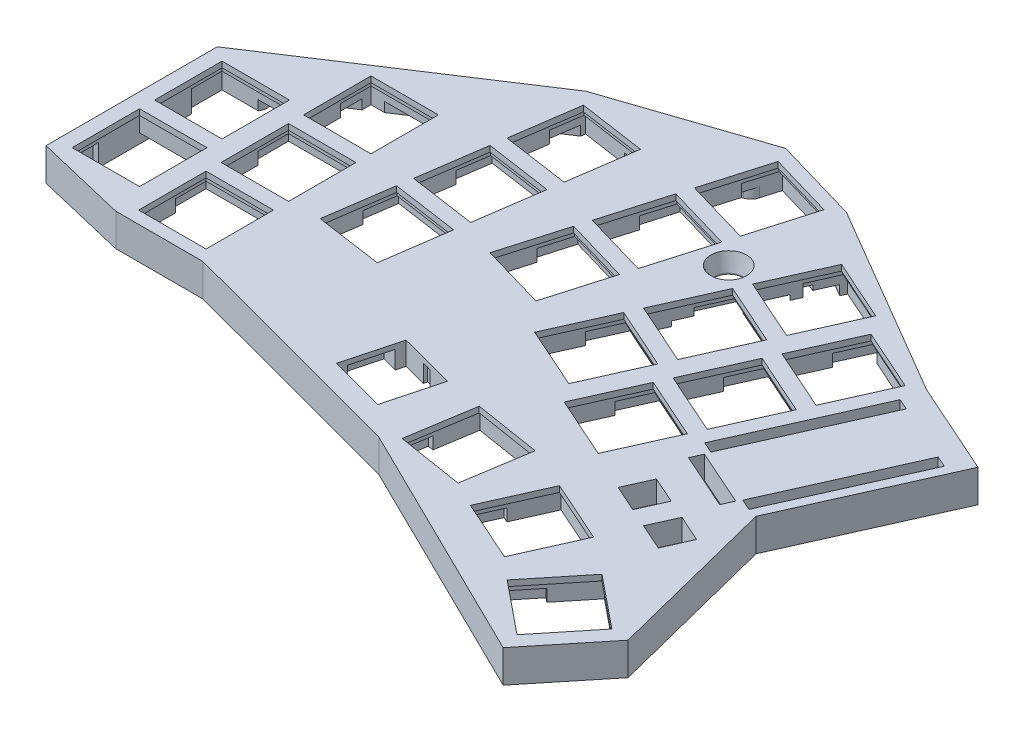
SolidWorks part; units mm, degrees
ref_plane "Front Plane" through (0, 0, 0) normal (0, 0, 1) x (1, 0, 0)
ref_plane "Top Plane" through (0, 0, 0) normal (0, 1, 0) x (1, 0, 0)
ref_plane "Right Plane" through (0, 0, 0) normal (1, 0, 0) x (0, 0, -1)
sketch "Ergogen Drawing" plane through (0, 0, 0) normal (0, 1, 0) x (1, 0, 0)
  line L0 (0.027, 17.9992) -> (18.027, 17.9992)
  line L1 (18.027, 17.9992) -> (18.027, -0.0008)
  line L2 (18.027, -0.0008) -> (0.027, -0.0008)
  line L3 (0.027, -0.0008) -> (0.027, 17.9992)
  line L4 (0.027, 34.9992) -> (18.027, 34.9992)
  line L5 (18.027, 34.9992) -> (18.027, 16.9992)
  line L6 (18.027, 16.9992) -> (0.027, 16.9992)
  line L7 (0.027, 16.9992) -> (0.027, 34.9992)
  line L8 (18.027, 15.9992) -> (36.027, 15.9992)
  line L9 (36.027, 15.9992) -> (36.027, -2.0008)
  line L10 (36.027, -2.0008) -> (18.027, -2.0008)
  line L11 (18.027, -2.0008) -> (18.027, 15.9992)
  line L12 (18.027, 32.9992) -> (36.027, 32.9992)
  line L13 (36.027, 32.9992) -> (36.027, 14.9992)
  line L14 (36.027, 14.9992) -> (18.027, 14.9992)
  line L15 (18.027, 14.9992) -> (18.027, 32.9992)
  line L16 (18.027, 49.9992) -> (36.027, 49.9992)
  line L17 (36.027, 49.9992) -> (36.027, 31.9992)
  line L18 (36.027, 31.9992) -> (18.027, 31.9992)
  line L19 (18.027, 31.9992) -> (18.027, 49.9992)
  line L20 (41.3768, 32.6051) -> (59.3329, 31.3495)
  line L21 (59.3329, 31.3495) -> (58.0773, 13.3933)
  line L22 (58.0773, 13.3933) -> (40.1211, 14.6489)
  line L23 (40.1211, 14.6489) -> (41.3768, 32.6051)
  line L24 (42.5626, 49.5637) -> (60.5188, 48.3081)
  line L25 (60.5188, 48.3081) -> (59.2631, 30.3519)
  line L26 (59.2631, 30.3519) -> (41.307, 31.6075)
  line L27 (41.307, 31.6075) -> (42.5626, 49.5637)
  line L28 (43.7485, 66.5223) -> (61.7046, 65.2667)
  line L29 (61.7046, 65.2667) -> (60.449, 47.3105)
  line L30 (60.449, 47.3105) -> (42.4929, 48.5661)
  line L31 (42.4929, 48.5661) -> (43.7485, 66.5223)
  line L32 (66.0898, 43.7082) -> (83.8507, 40.7838)
  line L33 (83.8507, 40.7838) -> (80.9263, 23.023)
  line L34 (80.9263, 23.023) -> (63.1655, 25.9473)
  line L35 (63.1655, 25.9473) -> (66.0898, 43.7082)
  line L36 (68.8517, 60.4823) -> (86.6126, 57.558)
  line L37 (86.6126, 57.558) -> (83.6882, 39.7971)
  line L38 (83.6882, 39.7971) -> (65.9274, 42.7215)
  line L39 (65.9274, 42.7215) -> (68.8517, 60.4823)
  line L40 (71.6136, 77.2565) -> (89.3745, 74.3321)
  line L41 (89.3745, 74.3321) -> (86.4501, 56.5713)
  line L42 (86.4501, 56.5713) -> (68.6893, 59.4956)
  line L43 (68.6893, 59.4956) -> (71.6136, 77.2565)
  line L44 (88.5581, 32.769) -> (105.9366, 28.0799)
  line L45 (105.9366, 28.0799) -> (101.2475, 10.7014)
  line L46 (101.2475, 10.7014) -> (83.869, 15.3905)
  line L47 (83.869, 15.3905) -> (88.5581, 32.769)
  line L48 (92.9866, 49.182) -> (110.3652, 44.4929)
  line L49 (110.3652, 44.4929) -> (105.6761, 27.1144)
  line L50 (105.6761, 27.1144) -> (88.2976, 31.8035)
  line L51 (88.2976, 31.8035) -> (92.9866, 49.182)
  line L52 (97.4152, 65.595) -> (114.7937, 60.906)
  line L53 (114.7937, 60.906) -> (110.1046, 43.5274)
  line L54 (110.1046, 43.5274) -> (92.7261, 48.2165)
  line L55 (92.7261, 48.2165) -> (97.4152, 65.595)
  line L56 (107.0448, 26.9674) -> (124.0477, 21.0597)
  line L57 (124.0477, 21.0597) -> (118.14, 4.0568)
  line L58 (118.14, 4.0568) -> (101.1371, 9.9645)
  line L59 (101.1371, 9.9645) -> (107.0448, 26.9674)
  line L60 (112.6243, 43.0257) -> (129.6273, 37.118)
  line L61 (129.6273, 37.118) -> (123.7195, 20.1151)
  line L62 (123.7195, 20.1151) -> (106.7166, 26.0228)
  line L63 (106.7166, 26.0228) -> (112.6243, 43.0257)
  line L64 (118.2039, 59.084) -> (135.2068, 53.1763)
  line L65 (135.2068, 53.1763) -> (129.299, 36.1734)
  line L66 (129.299, 36.1734) -> (112.2961, 42.0811)
  line L67 (112.2961, 42.0811) -> (118.2039, 59.084)
  line L68 (95.4197, 6.4051) -> (112.5714, 0.9445)
  line L69 (112.5714, 0.9445) -> (107.1108, -16.2072)
  line L70 (107.1108, -16.2072) -> (89.959, -10.7466)
  line L71 (89.959, -10.7466) -> (95.4197, 6.4051)
  line L72 (116.0129, -0.5249) -> (131.9353, -8.9198)
  line L73 (131.9353, -8.9198) -> (123.5404, -24.8423)
  line L74 (123.5404, -24.8423) -> (107.6179, -16.4473)
  line L75 (107.6179, -16.4473) -> (116.0129, -0.5249)
  line L76 (135.0644, -10.9721) -> (149.2602, -22.0392)
  line L77 (149.2602, -22.0392) -> (138.1931, -36.235)
  line L78 (138.1931, -36.235) -> (123.9973, -25.1679)
  line L79 (123.9973, -25.1679) -> (135.0644, -10.9721)
sketch "Layout Based on OG" plane through (0, 0, 0) normal (0, 1, 0) x (1, 0, 0)
  line L0 (0, 0) -> (0, 17) construction
  line L1 (0, 17) -> (18, 17) construction
  line L2 (18, 17) -> (18, 0) construction
  line L3 (18, 0) -> (0, 0) construction
  line L4 (2.05, 1.55) -> (2.05, 15.45)
  line L5 (2.05, 15.45) -> (15.95, 15.45)
  line L6 (15.95, 15.45) -> (15.95, 1.55)
  line L7 (15.95, 1.55) -> (2.05, 1.55)
  line L8 (109.1798, 58.6066) -> (27, -125.5436) construction
  line L9 (27, 46.7087) -> (27, -125.5436) construction
  line L10 (84.3863, 71.4039) -> (27, -125.5436) construction
  line L11 (54.2678, 62.3831) -> (27, -125.5436) construction
  line L12 (44.7261, 45.0233) -> (58.4821, 43.0274)
  line L13 (2.05, 18.55) -> (15.95, 18.55)
  line L14 (2.05, 18.55) -> (2.05, 32.45)
  line L15 (2.05, 32.45) -> (15.95, 32.45)
  line L16 (15.95, 18.55) -> (15.95, 32.45)
  line L17 (20.05, 31.2587) -> (33.95, 31.2587)
  line L18 (20.05, 31.2587) -> (20.05, 45.1587)
  line L19 (20.05, 45.1587) -> (33.95, 45.1587)
  line L20 (33.95, 31.2587) -> (33.95, 45.1587)
  line L21 (33.95, 28.1587) -> (20.05, 28.1587)
  line L22 (33.95, 28.1587) -> (33.95, 14.2587)
  line L23 (33.95, 14.2587) -> (20.05, 14.2587)
  line L24 (20.05, 28.1587) -> (20.05, 14.2587)
  line L25 (20.05, -2.7413) -> (33.95, -2.7413)
  line L26 (20.05, -2.7413) -> (20.05, 11.1587)
  line L27 (20.05, 11.1587) -> (33.95, 11.1587)
  line L28 (33.95, -2.7413) -> (33.95, 11.1587)
  line L29 (44.7261, 45.0233) -> (42.7302, 31.2674)
  line L30 (58.4821, 43.0274) -> (56.4861, 29.2714)
  line L31 (42.7302, 31.2674) -> (56.4861, 29.2714)
  line L32 (42.285, 28.1995) -> (56.041, 26.2036)
  line L33 (42.285, 28.1995) -> (40.2891, 14.4436)
  line L34 (56.041, 26.2036) -> (54.045, 12.4476)
  line L35 (40.2891, 14.4436) -> (54.045, 12.4476)
  line L36 (47.1672, 61.8472) -> (60.9232, 59.8512)
  line L37 (47.1672, 61.8472) -> (45.1712, 48.0912)
  line L38 (60.9232, 59.8512) -> (58.9272, 46.0953)
  line L39 (45.1712, 48.0912) -> (58.9272, 46.0953)
  line L40 (77.2802, 71.86) -> (90.6252, 67.9716)
  line L41 (77.2802, 71.86) -> (73.3917, 58.515)
  line L42 (90.6252, 67.9716) -> (86.7368, 54.6265)
  line L43 (73.3917, 58.515) -> (86.7368, 54.6265)
  line L44 (85.8695, 51.6503) -> (72.5245, 55.5388)
  line L45 (85.8695, 51.6503) -> (81.9811, 38.3053)
  line L46 (72.5245, 55.5388) -> (68.6361, 42.1937)
  line L47 (81.9811, 38.3053) -> (68.6361, 42.1937)
  line L48 (67.7688, 39.2175) -> (81.1139, 35.329)
  line L49 (67.7688, 39.2175) -> (63.8804, 25.8725)
  line L50 (81.1139, 35.329) -> (77.2254, 21.984)
  line L51 (63.8804, 25.8725) -> (77.2254, 21.984)
  line L52 (102.2015, 60.0235) -> (114.8949, 54.3589)
  line L53 (102.2015, 60.0235) -> (96.5369, 47.3301)
  line L54 (114.8949, 54.3589) -> (109.2302, 41.6655)
  line L55 (96.5369, 47.3301) -> (109.2302, 41.6655)
  line L56 (107.9669, 38.8346) -> (95.2735, 44.4992)
  line L57 (107.9669, 38.8346) -> (102.3023, 26.1412)
  line L58 (95.2735, 44.4992) -> (89.6089, 31.8058)
  line L59 (102.3023, 26.1412) -> (89.6089, 31.8058)
  line L60 (101.039, 23.3103) -> (88.3456, 28.9749)
  line L61 (101.039, 23.3103) -> (95.3744, 10.6169)
  line L62 (88.3456, 28.9749) -> (82.681, 16.2815)
  line L63 (95.3744, 10.6169) -> (82.681, 16.2815)
  line L64 (117.7053, 50.5958) -> (130.3987, 44.9312)
  line L65 (117.7053, 50.5958) -> (112.0407, 37.9024)
  line L66 (130.3987, 44.9312) -> (124.734, 32.2378)
  line L67 (112.0407, 37.9024) -> (124.734, 32.2378)
  line L68 (123.4707, 29.4069) -> (110.7773, 35.0715)
  line L69 (123.4707, 29.4069) -> (117.8061, 16.7135)
  line L70 (110.7773, 35.0715) -> (105.1127, 22.3782)
  line L71 (117.8061, 16.7135) -> (105.1127, 22.3782)
  line L72 (116.5428, 13.8826) -> (103.8494, 19.5473)
  line L73 (116.5428, 13.8826) -> (110.8782, 1.1892)
  line L74 (103.8494, 19.5473) -> (98.1848, 6.8539)
  line L75 (110.8782, 1.1892) -> (98.1848, 6.8539)
  line L76 (90.1692, -2.6429) -> (103.8962, -4.8292)
  line L77 (90.1692, -2.6429) -> (87.9829, -16.3699)
  line L78 (103.8962, -4.8292) -> (101.7099, -18.5562)
  line L79 (87.9829, -16.3699) -> (101.7099, -18.5562)
  line L80 (112.6329, -8.5638) -> (125.3263, -14.2284)
  line L81 (112.6329, -8.5638) -> (106.9683, -21.2572)
  line L82 (125.3263, -14.2284) -> (119.6617, -26.9218)
  line L83 (106.9683, -21.2572) -> (119.6617, -26.9218)
  line L84 (132.8305, -19.9983) -> (143.6253, -28.7552)
  line L85 (132.8305, -19.9983) -> (124.0737, -30.7931)
  line L86 (143.6253, -28.7552) -> (134.8684, -39.55)
  line L87 (124.0737, -30.7931) -> (134.8684, -39.55)
  line L88 (0, 0) -> (0, 34) construction
  line L89 (0, 34) -> (18, 46.7087) construction
  line L90 (18, 46.7087) -> (45.361, 63.6755) construction
  line L91 (45.361, 63.6755) -> (75.7456, 73.9216) construction
  line L92 (75.7456, 73.9216) -> (93.027, 68.8862) construction
  line L93 (93.027, 68.8862) -> (117.3986, 54.9389) construction
  line L94 (117.3986, 54.9389) -> (132.9024, 45.5112) construction
  line L95 (146.1938, -28.843) -> (135.484, -42.0452) construction
  line L96 (135.484, -42.0452) -> (85.7146, -17.5782) construction
  line L97 (0, 0) -> (18, -4.2913) construction
  line L98 (132.9024, 45.5112) -> (119.0465, 14.4627) construction
  line L99 (18, -4.2913) -> (36, -4.2913) construction
  line L100 (36, -4.2913) -> (85.7146, -17.5782) construction
  line L101 (119.0465, 14.4627) -> (137.3104, 6.3121) construction
  line L102 (137.3104, 6.3121) -> (151.1662, 37.3607) construction
  line L103 (151.1662, 37.3607) -> (132.9024, 45.5112) construction
  line L104 (146.1938, -28.843) -> (137.3104, 6.3121) construction
  line L105 (137.3104, 6.3121) -> (151.1662, 37.3607) construction
  line L106 (151.1662, 37.3607) -> (132.9024, 45.5112) construction
  line L107 (119.9597, 14.0551) -> (132.3892, 41.9075)
  line L108 (132.3892, 41.9075) -> (134.6722, 40.8887)
  line L109 (134.6722, 40.8887) -> (122.2427, 13.0363)
  line L110 (122.2427, 13.0363) -> (119.9597, 14.0551)
  line L111 (136.3972, 6.7197) -> (148.8267, 34.5721)
  line L112 (148.8267, 34.5721) -> (146.5437, 35.5909)
  line L113 (146.5437, 35.5909) -> (134.1142, 7.7385)
  line L114 (134.1142, 7.7385) -> (136.3972, 6.7197)
  line L115 (79.4058, -12.7868) -> (67.8127, -9.6883)
  line L116 (67.8127, -9.6883) -> (70.8336, 1.6149)
  line L117 (70.8336, 1.6149) -> (82.4267, -1.4835)
  line L118 (82.4267, -1.4835) -> (79.4058, -12.7868)
  line L119 (97.0327, -3.7361) -> (94.8464, -17.4631) construction
  line L120 (118.9913, -2.8379) -> (121.4364, 2.6412)
  line L121 (121.4364, 2.6412) -> (126.9156, 0.1961)
  line L122 (76.6302, 0.0657) -> (73.6092, -11.2375) construction
  line L123 (126.9156, 0.1961) -> (124.4704, -5.2831)
  line L124 (124.4704, -5.2831) -> (118.9913, -2.8379)
  line L125 (128.4611, -7.064) -> (130.9062, -1.5848)
  line L126 (130.9062, -1.5848) -> (136.3854, -4.03)
  line L127 (136.3854, -4.03) -> (133.9402, -9.5091)
  line L128 (133.9402, -9.5091) -> (128.4611, -7.064)
  line L137 (124.176, 1.4187) -> (121.7308, -4.0605) construction
  line L138 (133.6458, -2.8074) -> (131.2006, -8.2865) construction
  line L139 (126.7317, 7.1456) -> (128.1784, 10.3874) construction
  line L140 (135.0103, 42.8732) -> (147.795, 37.1678) construction
  line L141 (147.795, 37.1678) -> (133.1241, 4.2929) construction
  line L142 (133.1241, 4.2929) -> (120.3393, 9.9982) construction
  line L143 (120.3393, 9.9982) -> (135.0103, 42.8732) construction
  line L144 (120.9329, 9.7333) -> (121.9517, 12.0163)
  line L145 (121.9517, 12.0163) -> (133.5493, 6.8407)
  line L146 (133.5493, 6.8407) -> (132.5305, 4.5578)
  line L147 (132.5305, 4.5578) -> (120.9329, 9.7333)
  line L148 (126.9156, 0.1961) -> (140.3735, -5.8097) construction
  line L164 (-1, 34.5181) -> (-1, -0.7896)
  line L165 (-1, -0.7896) -> (17.8824, -5.2913)
  line L166 (17.8824, -5.2913) -> (35.8687, -5.2913)
  line L167 (35.8687, -5.2913) -> (85.3615, -18.5189)
  line L168 (85.3615, -18.5189) -> (135.7583, -43.2944)
  line L169 (135.7583, -43.2944) -> (147.2861, -29.0838)
  line L170 (147.2861, -29.0838) -> (138.3648, 6.2211)
  line L171 (138.3648, 6.2211) -> (152.487, 37.8664)
  line L172 (152.487, 37.8664) -> (133.3678, 46.3986)
  line L173 (133.3678, 46.3986) -> (117.9068, 55.8002) construction
  line L174 (117.9068, 55.8002) -> (93.4207, 69.8131) construction
  line L175 (93.4207, 69.8131) -> (75.7238, 74.9696)
  line L176 (75.7238, 74.9696) -> (44.9321, 64.5862)
  line L177 (44.9321, 64.5862) -> (17.4476, 47.5429) construction
  line L178 (17.4476, 47.5429) -> (-1, 34.5181) construction
  line L179 (-1, 34.5181) -> (44.9321, 64.5862)
  line L180 (133.3678, 46.3986) -> (93.4207, 69.8131)
  line L181 (27, -125.5436) -> (90.7493, 48.2155) construction
  circle A0 centre (143.0056, -24.3895) radius 2 construction
  circle A1 centre (143.0056, -24.3895) radius 1
  circle A2 centre (98.5143, -21.642) radius 2 construction
  circle A3 centre (98.5143, -21.642) radius 1
  circle A6 centre (17.05, -2.0087) radius 2 construction
  circle A7 centre (17.05, -2.0087) radius 1
  circle A8 centre (5.901, 35.45) radius 2 construction
  circle A9 centre (5.901, 35.45) radius 1
  circle A10 centre (72.7535, 70.802) radius 2 construction
  circle A11 centre (72.7535, 70.802) radius 1
  circle A12 centre (145.3286, 37.7757) radius 2 construction
  circle A13 centre (145.3286, 37.7757) radius 1
  circle A14 centre (90.7493, 48.2155) radius 3
  point P10 (110.8277, 18.1304)
  point P11 (117.7557, 33.6547)
  point P128 (75.1197, -5.5859)
  point P129 (95.9395, -10.5996)
  point P146 (127.7505, 9.4285)
  point P148 (128.1784, 10.3874)
  point P150 (122.9534, -1.3209)
  line B0 (18, 29.7087) -> (18, 46.7087) construction
  line B1 (18, 46.7087) -> (36, 46.7087) construction
  line B2 (36, 46.7087) -> (36, 29.7087) construction
  line B3 (36, 29.7087) -> (18, 29.7087) construction
  line B4 (20.05, 31.2587) -> (20.05, 45.1587) construction
  line B5 (20.05, 45.1587) -> (33.95, 45.1587) construction
  line B6 (33.95, 45.1587) -> (33.95, 31.2587) construction
  line B7 (33.95, 31.2587) -> (20.05, 31.2587) construction
  line B8 (18, 12.7087) -> (18, 29.7087) construction
  line B9 (18, 29.7087) -> (36, 29.7087) construction
  line B10 (36, 29.7087) -> (36, 12.7087) construction
  line B11 (36, 12.7087) -> (18, 12.7087) construction
  line B12 (20.05, 14.2587) -> (20.05, 28.1587) construction
  line B13 (20.05, 28.1587) -> (33.95, 28.1587) construction
  line B14 (33.95, 28.1587) -> (33.95, 14.2587) construction
  line B15 (33.95, 14.2587) -> (20.05, 14.2587) construction
  line B16 (18, -4.2913) -> (18, 12.7087) construction
  line B17 (18, 12.7087) -> (36, 12.7087) construction
  line B18 (36, 12.7087) -> (36, -4.2913) construction
  line B19 (36, -4.2913) -> (18, -4.2913) construction
  line B20 (20.05, -2.7413) -> (20.05, 11.1587) construction
  line B21 (20.05, 11.1587) -> (33.95, 11.1587) construction
  line B22 (33.95, 11.1587) -> (33.95, -2.7413) construction
  line B23 (33.95, -2.7413) -> (20.05, -2.7413) construction
  line B24 (42.9199, 46.8516) -> (45.361, 63.6755) construction
  line B25 (45.361, 63.6755) -> (63.1745, 61.0908) construction
  line B26 (63.1745, 61.0908) -> (60.7334, 44.267) construction
  line B27 (60.7334, 44.267) -> (42.9199, 46.8516) construction
  line B28 (45.1712, 48.0912) -> (47.1672, 61.8472) construction
  line B29 (47.1672, 61.8472) -> (60.9232, 59.8512) construction
  line B30 (60.9232, 59.8512) -> (58.9272, 46.0953) construction
  line B31 (58.9272, 46.0953) -> (45.1712, 48.0912) construction
  line B32 (40.4788, 30.0278) -> (42.9199, 46.8516) construction
  line B33 (42.9199, 46.8516) -> (60.7334, 44.267) construction
  line B34 (60.7334, 44.267) -> (58.2923, 27.4431) construction
  line B35 (58.2923, 27.4431) -> (40.4788, 30.0278) construction
  line B36 (42.7302, 31.2674) -> (44.7261, 45.0233) construction
  line B37 (44.7261, 45.0233) -> (58.4821, 43.0274) construction
  line B38 (58.4821, 43.0274) -> (56.4861, 29.2714) construction
  line B39 (56.4861, 29.2714) -> (42.7302, 31.2674) construction
  line B40 (38.0377, 13.204) -> (40.4788, 30.0278) construction
  line B41 (40.4788, 30.0278) -> (58.2923, 27.4431) construction
  line B42 (58.2923, 27.4431) -> (55.8512, 10.6193) construction
  line B43 (55.8512, 10.6193) -> (38.0377, 13.204) construction
  line B44 (40.2891, 14.4436) -> (42.285, 28.1995) construction
  line B45 (42.285, 28.1995) -> (56.041, 26.2036) construction
  line B46 (56.041, 26.2036) -> (54.045, 12.4476) construction
  line B47 (54.045, 12.4476) -> (40.2891, 14.4436) construction
  line B48 (70.99, 57.6004) -> (75.7456, 73.9216) construction
  line B49 (75.7456, 73.9216) -> (93.027, 68.8862) construction
  line B50 (93.027, 68.8862) -> (88.2713, 52.5649) construction
  line B51 (88.2713, 52.5649) -> (70.99, 57.6004) construction
  line B52 (73.3917, 58.515) -> (77.2802, 71.86) construction
  line B53 (77.2802, 71.86) -> (90.6252, 67.9716) construction
  line B54 (90.6252, 67.9716) -> (86.7368, 54.6265) construction
  line B55 (86.7368, 54.6265) -> (73.3917, 58.515) construction
  line B56 (66.2343, 41.2791) -> (70.99, 57.6004) construction
  line B57 (70.99, 57.6004) -> (88.2713, 52.5649) construction
  line B58 (88.2713, 52.5649) -> (83.5156, 36.2437) construction
  line B59 (83.5156, 36.2437) -> (66.2343, 41.2791) construction
  line B60 (68.6361, 42.1937) -> (72.5245, 55.5388) construction
  line B61 (72.5245, 55.5388) -> (85.8695, 51.6503) construction
  line B62 (85.8695, 51.6503) -> (81.9811, 38.3053) construction
  line B63 (81.9811, 38.3053) -> (68.6361, 42.1937) construction
  line B64 (61.4786, 24.9578) -> (66.2343, 41.2791) construction
  line B65 (66.2343, 41.2791) -> (83.5156, 36.2437) construction
  line B66 (83.5156, 36.2437) -> (78.76, 19.9224) construction
  line B67 (78.76, 19.9224) -> (61.4786, 24.9578) construction
  line B68 (63.8804, 25.8725) -> (67.7688, 39.2175) construction
  line B69 (67.7688, 39.2175) -> (81.1139, 35.329) construction
  line B70 (81.1139, 35.329) -> (77.2254, 21.984) construction
  line B71 (77.2254, 21.984) -> (63.8804, 25.8725) construction
  line B72 (80.1772, 15.7015) -> (87.1052, 31.2258) construction
  line B73 (87.1052, 31.2258) -> (103.5427, 23.8903) construction
  line B74 (103.5427, 23.8903) -> (96.6147, 8.366) construction
  line B75 (96.6147, 8.366) -> (80.1772, 15.7015) construction
  line B76 (82.681, 16.2815) -> (88.3456, 28.9749) construction
  line B77 (88.3456, 28.9749) -> (101.039, 23.3103) construction
  line B78 (101.039, 23.3103) -> (95.3744, 10.6169) construction
  line B79 (95.3744, 10.6169) -> (82.681, 16.2815) construction
  line B80 (87.1052, 31.2258) -> (94.0331, 46.7501) construction
  line B81 (94.0331, 46.7501) -> (110.4706, 39.4146) construction
  line B82 (110.4706, 39.4146) -> (103.5427, 23.8903) construction
  line B83 (103.5427, 23.8903) -> (87.1052, 31.2258) construction
  line B84 (89.6089, 31.8058) -> (95.2735, 44.4992) construction
  line B85 (95.2735, 44.4992) -> (107.9669, 38.8346) construction
  line B86 (107.9669, 38.8346) -> (102.3023, 26.1412) construction
  line B87 (102.3023, 26.1412) -> (89.6089, 31.8058) construction
  line B88 (94.0331, 46.7501) -> (100.9611, 62.2744) construction
  line B89 (100.9611, 62.2744) -> (117.3986, 54.9389) construction
  line B90 (117.3986, 54.9389) -> (110.4706, 39.4146) construction
  line B91 (110.4706, 39.4146) -> (94.0331, 46.7501) construction
  line B92 (96.5369, 47.3301) -> (102.2015, 60.0235) construction
  line B93 (102.2015, 60.0235) -> (114.8949, 54.3589) construction
  line B94 (114.8949, 54.3589) -> (109.2302, 41.6655) construction
  line B95 (109.2302, 41.6655) -> (96.5369, 47.3301) construction
  line B96 (109.5369, 37.3224) -> (116.4649, 52.8467) construction
  line B97 (116.4649, 52.8467) -> (132.9024, 45.5112) construction
  line B98 (132.9024, 45.5112) -> (125.9744, 29.9869) construction
  line B99 (125.9744, 29.9869) -> (109.5369, 37.3224) construction
  line B100 (112.0407, 37.9024) -> (117.7053, 50.5958) construction
  line B101 (117.7053, 50.5958) -> (130.3987, 44.9312) construction
  line B102 (130.3987, 44.9312) -> (124.734, 32.2378) construction
  line B103 (124.734, 32.2378) -> (112.0407, 37.9024) construction
  line B104 (102.609, 21.7981) -> (109.5369, 37.3224) construction
  line B105 (109.5369, 37.3224) -> (125.9744, 29.9869) construction
  line B106 (125.9744, 29.9869) -> (119.0465, 14.4627) construction
  line B107 (119.0465, 14.4627) -> (102.609, 21.7981) construction
  line B108 (105.1127, 22.3782) -> (110.7773, 35.0715) construction
  line B109 (110.7773, 35.0715) -> (123.4707, 29.4069) construction
  line B110 (123.4707, 29.4069) -> (117.8061, 16.7135) construction
  line B111 (117.8061, 16.7135) -> (105.1127, 22.3782) construction
  line B112 (95.6811, 6.2738) -> (102.609, 21.7981) construction
  line B113 (102.609, 21.7981) -> (119.0465, 14.4627) construction
  line B114 (119.0465, 14.4627) -> (112.1185, -1.0616) construction
  line B115 (112.1185, -1.0616) -> (95.6811, 6.2738) construction
  line B116 (98.1848, 6.8539) -> (103.8494, 19.5473) construction
  line B117 (103.8494, 19.5473) -> (116.5428, 13.8826) construction
  line B118 (116.5428, 13.8826) -> (110.8782, 1.1892) construction
  line B119 (110.8782, 1.1892) -> (98.1848, 6.8539) construction
  line B120 (104.4646, -21.8372) -> (111.3925, -6.3129) construction
  line B121 (111.3925, -6.3129) -> (127.83, -13.6484) construction
  line B122 (127.83, -13.6484) -> (120.9021, -29.1727) construction
  line B123 (120.9021, -29.1727) -> (104.4646, -21.8372) construction
  line B124 (106.9683, -21.2572) -> (112.6329, -8.5638) construction
  line B125 (112.6329, -8.5638) -> (125.3263, -14.2284) construction
  line B126 (125.3263, -14.2284) -> (119.6617, -26.9218) construction
  line B127 (119.6617, -26.9218) -> (106.9683, -21.2572) construction
  line B128 (85.7146, -17.5782) -> (88.3885, -0.7898) construction
  line B129 (88.3885, -0.7898) -> (106.1645, -3.621) construction
  line B130 (106.1645, -3.621) -> (103.4906, -20.4094) construction
  line B131 (103.4906, -20.4094) -> (85.7146, -17.5782) construction
  line B132 (87.9829, -16.3699) -> (90.1692, -2.6429) construction
  line B133 (90.1692, -2.6429) -> (103.8962, -4.8292) construction
  line B134 (103.8962, -4.8292) -> (101.7099, -18.5562) construction
  line B135 (101.7099, -18.5562) -> (87.9829, -16.3699) construction
  line B136 (121.5051, -30.7054) -> (132.215, -17.5031) construction
  line B137 (132.215, -17.5031) -> (146.1938, -28.843) construction
  line B138 (146.1938, -28.843) -> (135.484, -42.0452) construction
  line B139 (135.484, -42.0452) -> (121.5051, -30.7054) construction
  line B140 (124.0737, -30.7931) -> (132.8305, -19.9983) construction
  line B141 (132.8305, -19.9983) -> (143.6253, -28.7552) construction
  line B142 (143.6253, -28.7552) -> (134.8684, -39.55) construction
  line B143 (134.8684, -39.55) -> (124.0737, -30.7931) construction
  line B144 (0, 17) -> (0, 34) construction
  line B145 (0, 34) -> (18, 34) construction
  line B146 (18, 34) -> (18, 17) construction
  line B147 (18, 17) -> (0, 17) construction
  line B148 (2.05, 18.55) -> (2.05, 32.45) construction
  line B149 (2.05, 32.45) -> (15.95, 32.45) construction
  line B150 (15.95, 32.45) -> (15.95, 18.55) construction
  line B151 (15.95, 18.55) -> (2.05, 18.55) construction
  dimension "D46" = 4
  dimension "D47" = 2
  dimension "D48" = 3
  dimension "D52" = 4
  dimension "D53" = 2
  dimension "D54" = 4
  dimension "D55" = 2
  dimension "D57" = 4
  dimension "D58" = 2
  dimension "D60" = 4
  dimension "D61" = 2
  dimension "D63" = 4
  dimension "D64" = 2
  dimension "D51" = 3
  dimension "D83" = 6
  dimension "D1" = 18
  dimension "D2" = 17
  dimension "D3" = 13.9
  dimension "D4" = 13.9
  dimension "D5" = 2.05
  dimension "D6" = 1.55
  dimension "D7" = 205.1378
  dimension "D8" = 201.6553
  dimension "D9" = 189.8947
  dimension "D10" = 8.256
  dimension "D11" = 15
  dimension "D12" = 15
  dimension "D13" = 1.4278
  dimension "D14" = 0.974
  dimension "D15" = 1.5327
  dimension "D16" = 0.6031
  dimension "D17" = 5.9541
  dimension "D18" = 2.5593
  dimension "D19" = 7.805
  dimension "D20" = 7.989
  dimension "D21" = 172.2524
  dimension "D22" = 2.2911
  dimension "D23" = 4.2913
  dimension "D24" = 34
  dimension "D25" = 20
  dimension "D26" = 30.5
  dimension "D27" = 2.5
  dimension "D28" = 1
  dimension "D29" = 2.5
  dimension "D30" = 30.5
  dimension "D31" = 18
  dimension "D32" = 11.7
  dimension "D33" = 12
  dimension "D34" = 3
  dimension "D35" = 21.415
  dimension "D36" = 6
  dimension "D37" = 6
  dimension "D38" = 6
  dimension "D39" = 6
  dimension "D40" = 14
  dimension "D41" = 36
  dimension "D42" = 12.7
  dimension "D43" = 2.5
  dimension "D44" = 9.27
  dimension "D45" = 4.37
  dimension "D49" = 3
  dimension "D50" = 3
  dimension "D56" = 3
  dimension "D59" = 3
  dimension "D62" = 3
  dimension "D65" = 3
  dimension "D66" = 3
  dimension "D67" = 1
  dimension "D68" = 1
  dimension "D69" = 1
  dimension "D70" = 1
  dimension "D71" = 1
  dimension "D72" = 1
  dimension "D73" = 1
  dimension "D74" = 1
  dimension "D75" = 1
  dimension "D76" = 1
  dimension "D77" = 1
  dimension "D78" = 1
  dimension "D79" = 1
  dimension "D80" = 1
  dimension "D81" = 1
  dimension "D82" = 3.902
sketch_block_instance "Block-ChocSwitchCutout-3"
sketch_block "Block-ChocSwitchCutout" parameters "D1"=18, "D2"=17, "D3"=13.9, "D4"=13.9, "D5"=2.05, "D6"=1.55
sketch_block_instance "Block-ChocSwitchCutout-4"
sketch_block_instance "Block-ChocSwitchCutout-5"
sketch_block_instance "Block-ChocSwitchCutout-6"
sketch_block_instance "Block-ChocSwitchCutout-7"
sketch_block_instance "Block-ChocSwitchCutout-8"
sketch_block_instance "Block-ChocSwitchCutout-9"
sketch_block_instance "Block-ChocSwitchCutout-10"
sketch_block_instance "Block-ChocSwitchCutout-11"
sketch_block_instance "Block-ChocSwitchCutout-20"
sketch_block_instance "Block-ChocSwitchCutout-23"
sketch_block_instance "Block-ChocSwitchCutout-24"
sketch_block_instance "Block-ChocSwitchCutout-27"
sketch_block_instance "Block-ChocSwitchCutout-28"
sketch_block_instance "Block-ChocSwitchCutout-29"
sketch_block_instance "Block-ChocSwitchCutout-32"
sketch_block_instance "Block-ChocSwitchCutout-33"
sketch_block_instance "Block-ChocSwitchCutout-34"
sketch_block_instance "Block-ChocSwitchCutout-37"
other "AlignGroup1"
extrude "Top Plate" add sketch "Layout Based on OG" along normal blind 1.2 contours L105 L106 L94 L93 L92 L91 L90 L89 L88 L97 L99 L100 L96 L95 L104 L73 L75 L74 L72 L69 L71 L70 L68 L61 L63 L62 L60 L57 L59 L58 L56 L45 L47 L46 L44 L6 L7 L4 L5 L16 L13 L14 L15 | A9 | A7 | A3 | A1 | A13 | A11 region at (81.1816, 0, -18.7966) region at (143.0056, 0, 24.3895) region at (98.5143, 0, 21.642) region at (17.05, 0, 2.0087) region at (5.901, 0, -35.45) region at (72.7535, 0, -70.802) region at (145.3286, 0, -37.7757)
sketch "Sketch1" plane through (0, 0, 0) normal (0, -1, 0) x (1, 0, 0)
  line L0 (124.9363, -31.7095) -> (130.927, -45.1335)
  line L1 (130.927, -45.1335) -> (117.503, -51.1241)
  line L2 (117.503, -51.1241) -> (111.5124, -37.7002)
  line L3 (111.5124, -37.7002) -> (124.9363, -31.7095)
  line L4 (118.0084, -16.1852) -> (123.999, -29.6092)
  line L5 (117.7053, -50.5958) -> (130.3987, -44.9312) construction
  line L6 (123.999, -29.6092) -> (110.5751, -35.5998)
  line L7 (117.7053, -50.5958) -> (112.0407, -37.9024) construction
  line L8 (110.5751, -35.5998) -> (104.5844, -22.1759)
  line L9 (104.5844, -22.1759) -> (118.0084, -16.1852)
  line L10 (123.4707, -29.4069) -> (117.8061, -16.7135) construction
  line L11 (111.0804, -0.661) -> (117.0711, -14.0849)
  line L12 (117.8061, -16.7135) -> (105.1127, -22.3782) construction
  line L13 (117.0711, -14.0849) -> (103.6471, -20.0755)
  line L14 (103.6471, -20.0755) -> (97.6565, -6.6516)
  line L15 (97.6565, -6.6516) -> (111.0804, -0.661)
  line L16 (103.8494, -19.5473) -> (98.1848, -6.8539) construction
  line L17 (110.8782, -1.1892) -> (98.1848, -6.8539) construction
  line L18 (95.5766, -10.0886) -> (101.5673, -23.5126)
  line L19 (101.5673, -23.5126) -> (88.1433, -29.5032)
  line L20 (88.1433, -29.5032) -> (82.1527, -16.0793)
  line L21 (82.1527, -16.0793) -> (95.5766, -10.0886)
  line L22 (101.039, -23.3103) -> (88.3456, -28.9749) construction
  line L23 (101.039, -23.3103) -> (95.3744, -10.6169) construction
  line L24 (102.5046, -25.6129) -> (108.4952, -39.0369)
  line L25 (108.4952, -39.0369) -> (95.0713, -45.0275)
  line L26 (95.0713, -45.0275) -> (89.0806, -31.6036)
  line L27 (89.0806, -31.6036) -> (102.5046, -25.6129)
  line L28 (102.3023, -26.1412) -> (89.6089, -31.8058) construction
  line L29 (95.2735, -44.4992) -> (89.6089, -31.8058) construction
  line L30 (109.4325, -41.1372) -> (115.4231, -54.5612)
  line L31 (115.4231, -54.5612) -> (101.9992, -60.5518)
  line L32 (101.9992, -60.5518) -> (96.0086, -47.1279)
  line L33 (96.0086, -47.1279) -> (109.4325, -41.1372)
  line L34 (102.2015, -60.0235) -> (114.8949, -54.3589) construction
  line L35 (114.8949, -54.3589) -> (109.2302, -41.6655) construction
  line L36 (119.864, 27.4501) -> (125.8546, 14.0261)
  line L37 (125.8546, 14.0261) -> (112.4307, 8.0355)
  line L38 (112.4307, 8.0355) -> (106.44, 21.4594)
  line L39 (106.44, 21.4594) -> (119.864, 27.4501)
  line L40 (125.3263, 14.2284) -> (119.6617, 26.9218) construction
  line L41 (106.9683, 21.2572) -> (119.6617, 26.9218) construction
  line L42 (144.1879, 28.6966) -> (134.9271, 40.1126)
  line L43 (134.9271, 40.1126) -> (123.511, 30.8517)
  line L44 (123.511, 30.8517) -> (132.7719, 19.4357)
  line L45 (132.7719, 19.4357) -> (144.1879, 28.6966)
  line L46 (143.6253, 28.7552) -> (134.8684, 39.55) construction
  line L47 (132.8305, 19.9983) -> (143.6253, 28.7552) construction
  line L48 (132.8305, 19.9983) -> (124.0737, 30.7931) construction
  line L49 (104.3541, 4.4971) -> (102.042, 19.0142)
  line L50 (102.042, 19.0142) -> (87.5249, 16.702)
  line L51 (87.5249, 16.702) -> (89.8371, 2.185)
  line L52 (89.8371, 2.185) -> (104.3541, 4.4971)
  line L61 (86.3655, -51.9224) -> (82.2532, -37.8093)
  line L62 (103.8962, 4.8292) -> (101.7099, 18.5562) construction
  line L63 (82.2532, -37.8093) -> (68.1401, -41.9216)
  line L64 (87.9829, 16.3699) -> (101.7099, 18.5562) construction
  line L65 (91.1211, -68.2437) -> (87.0089, -54.1306)
  line L66 (87.0089, -54.1306) -> (72.8958, -58.2429)
  line L67 (72.8958, -58.2429) -> (77.008, -72.3559)
  line L68 (77.008, -72.3559) -> (91.1211, -68.2437)
  line L69 (61.3764, -60.1896) -> (59.2656, -45.642)
  line L70 (59.2656, -45.642) -> (44.718, -47.7528)
  line L71 (44.718, -47.7528) -> (46.8288, -62.3005)
  line L72 (46.8288, -62.3005) -> (61.3764, -60.1896)
  line L73 (34.35, -45.5587) -> (34.35, -30.8587)
  line L74 (34.35, -30.8587) -> (19.65, -30.8587)
  line L75 (19.65, -30.8587) -> (19.65, -45.5587)
  line L76 (19.65, -45.5587) -> (34.35, -45.5587)
  line L77 (90.6252, -67.9716) -> (86.7368, -54.6265) construction
  line L78 (47.1672, -61.8472) -> (45.1712, -48.0912) construction
  line L79 (33.95, -31.2587) -> (33.95, -45.1587) construction
  line L80 (73.3917, -58.515) -> (86.7368, -54.6265) construction
  line L81 (60.9232, -59.8512) -> (58.9272, -46.0953) construction
  line L82 (45.1712, -48.0912) -> (58.9272, -46.0953) construction
  line L83 (68.1401, -41.9216) -> (72.2524, -56.0347)
  line L84 (20.05, -31.2587) -> (33.95, -31.2587) construction
  line L85 (72.2524, -56.0347) -> (86.3655, -51.9224)
  line L86 (85.8695, -51.6503) -> (81.9811, -38.3053) construction
  line L87 (81.9811, -38.3053) -> (68.6361, -42.1937) construction
  line L88 (81.6098, -35.6012) -> (77.4976, -21.4881)
  line L89 (77.4976, -21.4881) -> (63.3845, -25.6003)
  line L90 (63.3845, -25.6003) -> (67.4967, -39.7134)
  line L91 (67.4967, -39.7134) -> (81.6098, -35.6012)
  line L92 (81.1139, -35.329) -> (77.2254, -21.984) construction
  line L93 (63.8804, -25.8725) -> (77.2254, -21.984) construction
  line L94 (58.9353, -43.3658) -> (56.8245, -28.8181)
  line L95 (56.8245, -28.8181) -> (42.2769, -30.929)
  line L96 (42.2769, -30.929) -> (44.3877, -45.4766)
  line L97 (44.3877, -45.4766) -> (58.9353, -43.3658)
  line L98 (58.4821, -43.0274) -> (56.4861, -29.2714) construction
  line L99 (42.7302, -31.2674) -> (56.4861, -29.2714) construction
  line L100 (56.4943, -26.542) -> (54.3834, -11.9943)
  line L101 (54.3834, -11.9943) -> (39.8358, -14.1052)
  line L102 (39.8358, -14.1052) -> (41.9466, -28.6528)
  line L103 (41.9466, -28.6528) -> (56.4943, -26.542)
  line L104 (56.041, -26.2036) -> (54.045, -12.4476) construction
  line L105 (40.2891, -14.4436) -> (54.045, -12.4476) construction
  line L106 (34.35, -28.5587) -> (34.35, -13.8587)
  line L107 (34.35, -13.8587) -> (19.65, -13.8587)
  line L108 (19.65, -13.8587) -> (19.65, -28.5587)
  line L109 (19.65, -28.5587) -> (34.35, -28.5587)
  line L110 (33.95, -28.1587) -> (33.95, -14.2587) construction
  line L111 (33.95, -14.2587) -> (20.05, -14.2587) construction
  line L112 (34.35, -11.5587) -> (34.35, 3.1413)
  line L113 (34.35, 3.1413) -> (19.65, 3.1413)
  line L114 (19.65, 3.1413) -> (19.65, -11.5587)
  line L115 (19.65, -11.5587) -> (34.35, -11.5587)
  line L116 (20.05, 2.7413) -> (33.95, 2.7413) construction
  line L117 (20.05, 2.7413) -> (20.05, -11.1587) construction
  line L118 (16.35, -15.85) -> (16.35, -1.15)
  line L119 (16.35, -1.15) -> (1.65, -1.15)
  line L120 (1.65, -1.15) -> (1.65, -15.85)
  line L121 (1.65, -15.85) -> (16.35, -15.85)
  line L122 (2.05, -1.55) -> (2.05, -15.45) construction
  line L123 (15.95, -1.55) -> (2.05, -1.55) construction
  line L124 (16.35, -32.85) -> (16.35, -18.15)
  line L125 (16.35, -18.15) -> (1.65, -18.15)
  line L126 (1.65, -18.15) -> (1.65, -32.85)
  line L127 (1.65, -32.85) -> (16.35, -32.85)
  line L128 (2.05, -18.55) -> (2.05, -32.45) construction
  line L129 (2.05, -18.55) -> (15.95, -18.55) construction
  dimension "D1" = 14.7
  dimension "D2" = 14.7
  dimension "D3" = 0.4
  dimension "D4" = 0.4
  dimension "D5" = 14.7
  dimension "D6" = 14.7
  dimension "D7" = 0.4
  dimension "D8" = 0.4
  dimension "D9" = 14.7
  dimension "D10" = 14.7
  dimension "D11" = 0.4
  dimension "D12" = 0.4
  dimension "D13" = 14.7
  dimension "D14" = 14.7
  dimension "D15" = 0.4
  dimension "D16" = 0.4
  dimension "D17" = 14.7
  dimension "D18" = 14.7
  dimension "D19" = 0.4
  dimension "D20" = 0.4
  dimension "D21" = 14.7
  dimension "D22" = 0.4
  dimension "D23" = 0.4
  dimension "D24" = 14.7
  dimension "D25" = 14.7
  dimension "D26" = 14.7
  dimension "D27" = 0.4
  dimension "D28" = 0.4
  dimension "D29" = 14.7
  dimension "D30" = 14.7
  dimension "D31" = 0.4
  dimension "D32" = 0.4
  dimension "D33" = 14.7
  dimension "D34" = 14.7
  dimension "D35" = 0.4
  dimension "D36" = 0.4
  dimension "D37" = 0.4
  dimension "D38" = 0.4
  dimension "D39" = 14.7
  dimension "D40" = 14.7
  dimension "D41" = 0.4
  dimension "D42" = 0.4
  dimension "D43" = 14.7
  dimension "D44" = 14.7
  dimension "D45" = 14.7
  dimension "D46" = 0.4
  dimension "D47" = 0.4
  dimension "D48" = 14.7
  dimension "D49" = 14.7
  dimension "D50" = 14.7
  dimension "D51" = 0.4
  dimension "D52" = 0.4
  dimension "D53" = 14.7
  dimension "D54" = 14.7
  dimension "D55" = 0.4
  dimension "D56" = 0.4
  dimension "D57" = 14.7
  dimension "D58" = 14.7
  dimension "D59" = 0.4
  dimension "D60" = 0.4
  dimension "D61" = 14.7
  dimension "D62" = 14.7
  dimension "D63" = 0.4
  dimension "D64" = 0.4
  dimension "D65" = 14.7
  dimension "D66" = 14.7
  dimension "D67" = 0.4
  dimension "D68" = 0.4
  dimension "D69" = 14.7
  dimension "D70" = 14.7
  dimension "D71" = 0.4
  dimension "D72" = 0.4
  dimension "D73" = 14.7
  dimension "D74" = 14.7
  dimension "D75" = 0.4
  dimension "D76" = 0.4
  dimension "D77" = 14.7
  dimension "D78" = 14.7
  dimension "D79" = 0.4
  dimension "D80" = 0.4
extrude "Boss-Extrude2" add sketch "Layout Based on OG<7>" against normal blind 5.5 contours L172 L180 L175 L176 L179 L164 L165 L166 L167 L168 L169 L170 L171 A13 A11 A9 A7 A3 A1 L146 L147 L144 L145 L127 L128 L125 L126 L123 L124 L120 L121 L117 L118 L115 L116 L109 L110 L107 L108 region at (81.1816, 0, -18.7966)
sketch "Layout Based on OG<7>" plane through (0, 0, 0) normal (0, 1, 0) x (1, 0, 0) same geometry as "Layout Based on OG"
extrude "Cut-Extrude1" cut sketch "Sketch1" along normal blind 5.5
sketch "Sketch4" plane through (0, -5.5, 0) normal (0, -1, 0) x (1, 0, 0)
  line L0 (74.3817, 12.2203) -> (77.7899, -0.5321)
  line L1 (77.7899, -0.5321) -> (75.8577, -1.0485)
  line L2 (75.8577, -1.0485) -> (72.4495, 11.7039)
  line L3 (72.4495, 11.7039) -> (74.3817, 12.2203)
  line L4 (67.8127, 9.6883) -> (70.8336, -1.6149) construction
  line L6 (79.4058, 12.7868) -> (67.8127, 9.6883) construction
  line L8 (82.4267, 1.4835) -> (79.4058, 12.7868) construction
  line L9 (83.0232, 11.8386) -> (85.0888, 4.1099)
  line L10 (85.0888, 4.1099) -> (76.394, 1.7861)
  line L11 (76.394, 1.7861) -> (67.2162, -0.6668)
  line L12 (67.2162, -0.6668) -> (65.1505, 7.0619)
  line L14 (83.0232, 11.8386) -> (74.3284, 9.5148)
  line L15 (74.3284, 9.5148) -> (65.1505, 7.0619)
  dimension "D1" = 2
  dimension "D2" = 13.2
  dimension "D3" = 0.75
  dimension "D4" = 5
  dimension "D5" = 9
  dimension "D6" = 9.5
  dimension "D7" = 3.25
  dimension "D8" = 8
  dimension "D9" = 1.85
  dimension "D10" = 9
extrude "Cut-Extrude2" cut sketch "Sketch4" against normal blind 5.7 contours L9 L14 L0 L10 | L2 L15 L12 L11 | L10 L11 L2 L1 L0 | L15 L14 L0 L3 L2 region at (73.7512, -5.5, 10.7062) region at (80.0709, -5.5, 6.9092) region at (76.4882, -5.5, 0.4656) region at (70.1685, -5.5, 4.2626)
sketch "Sketch5" plane through (0, -5.5, 0) normal (0, -1, 0) x (1, 0, 0)
  line L0 (90.4768, -61.9215) -> (92.5469, -69.0261)
  line L1 (92.5469, -69.0261) -> (76.2257, -73.7817)
  line L2 (76.2257, -73.7817) -> (74.1556, -66.6772)
  line L3 (74.1556, -66.6772) -> (90.4768, -61.9215)
  line L4 (91.1211, -68.2437) -> (87.0089, -54.1306) construction
  line L5 (80.9655, -29.279) -> (83.0356, -36.3835)
  line L6 (83.0356, -36.3835) -> (66.7143, -41.1392)
  line L7 (66.7143, -41.1392) -> (64.6442, -34.0347)
  line L8 (64.6442, -34.0347) -> (80.9655, -29.279)
  line L9 (72.2524, -56.0347) -> (86.3655, -51.9224) construction
  line L10 (77.008, -72.3559) -> (91.1211, -68.2437) construction
  line L11 (85.7211, -45.6003) -> (87.7913, -52.7048)
  line L12 (87.7913, -52.7048) -> (71.47, -57.4605)
  line L13 (71.47, -57.4605) -> (69.3999, -50.3559)
  line L14 (69.3999, -50.3559) -> (85.7211, -45.6003)
  line L15 (68.1401, -41.9216) -> (72.2524, -56.0347) construction
  line L16 (81.6098, -35.6012) -> (77.4976, -21.4881) construction
  line L17 (67.4967, -39.7134) -> (81.6098, -35.6012) construction
  line L18 (113.9263, -48.385) -> (116.942, -55.1427)
  line L19 (116.942, -55.1427) -> (101.4177, -62.0706)
  line L20 (101.4177, -62.0706) -> (98.402, -55.313)
  line L21 (98.402, -55.313) -> (113.9263, -48.385)
  line L22 (96.0086, -47.1279) -> (101.9992, -60.5518) construction
  line L23 (106.9983, -32.8608) -> (110.014, -39.6184)
  line L24 (110.014, -39.6184) -> (94.4897, -46.5463)
  line L25 (94.4897, -46.5463) -> (91.474, -39.7887)
  line L26 (91.474, -39.7887) -> (106.9983, -32.8608)
  line L27 (100.0704, -17.3365) -> (103.0861, -24.0941)
  line L28 (103.0861, -24.0941) -> (87.5618, -31.022)
  line L29 (87.5618, -31.022) -> (84.5461, -24.2644)
  line L30 (84.5461, -24.2644) -> (100.0704, -17.3365)
  line L31 (115.5742, -7.9088) -> (118.5899, -14.6664)
  line L32 (118.5899, -14.6664) -> (103.0656, -21.5944)
  line L33 (103.0656, -21.5944) -> (100.0499, -14.8367)
  line L34 (100.0499, -14.8367) -> (115.5742, -7.9088)
  line L35 (122.5021, -23.4331) -> (125.5178, -30.1907)
  line L36 (125.5178, -30.1907) -> (109.9935, -37.1187)
  line L37 (109.9935, -37.1187) -> (106.9778, -30.361)
  line L38 (106.9778, -30.361) -> (122.5021, -23.4331)
  line L39 (129.4301, -38.9574) -> (132.4458, -45.715)
  line L40 (132.4458, -45.715) -> (116.9215, -52.6429)
  line L41 (116.9215, -52.6429) -> (113.9058, -45.8853)
  line L42 (113.9058, -45.8853) -> (129.4301, -38.9574)
  line L43 (130.927, -45.1335) -> (124.9363, -31.7095) construction
  line L44 (117.503, -51.1241) -> (130.927, -45.1335) construction
  line L45 (115.4231, -54.5612) -> (109.4325, -41.1372) construction
  line L46 (101.9992, -60.5518) -> (115.4231, -54.5612) construction
  line L47 (89.0806, -31.6036) -> (95.0713, -45.0275) construction
  line L48 (95.0713, -45.0275) -> (108.4952, -39.0369) construction
  line L49 (88.1433, -29.5032) -> (101.5673, -23.5126) construction
  line L50 (101.5673, -23.5126) -> (95.5766, -10.0886) construction
  line L51 (117.0711, -14.0849) -> (111.0804, -0.661) construction
  line L52 (103.6471, -20.0755) -> (117.0711, -14.0849) construction
  line L53 (123.999, -29.6092) -> (118.0084, -16.1852) construction
  line L54 (110.5751, -35.5998) -> (123.999, -29.6092) construction
  line L55 (61.6171, -53.8393) -> (62.6797, -61.1626)
  line L56 (62.6797, -61.1626) -> (45.8558, -63.6037)
  line L57 (45.8558, -63.6037) -> (44.7932, -56.2804)
  line L58 (44.7932, -56.2804) -> (61.6171, -53.8393)
  line L59 (61.3764, -60.1896) -> (59.2656, -45.642) construction
  line L60 (59.176, -37.0154) -> (60.2386, -44.3387)
  line L61 (60.2386, -44.3387) -> (43.4147, -46.7798)
  line L62 (43.4147, -46.7798) -> (42.3521, -39.4565)
  line L63 (42.3521, -39.4565) -> (59.176, -37.0154)
  line L64 (56.7349, -20.1916) -> (57.7975, -27.5149)
  line L65 (57.7975, -27.5149) -> (40.9736, -29.956)
  line L66 (40.9736, -29.956) -> (39.911, -22.6327)
  line L67 (39.911, -22.6327) -> (56.7349, -20.1916)
  line L68 (35.5, -39.3087) -> (35.5, -46.7087)
  line L69 (35.5, -46.7087) -> (18.5, -46.7087)
  line L70 (18.5, -46.7087) -> (18.5, -39.3087)
  line L71 (18.5, -39.3087) -> (35.5, -39.3087)
  line L72 (34.35, -45.5587) -> (34.35, -30.8587) construction
  line L73 (35.5, -22.3087) -> (35.5, -29.7087)
  line L74 (35.5, -29.7087) -> (18.5, -29.7087)
  line L75 (18.5, -29.7087) -> (18.5, -22.3087)
  line L76 (18.5, -22.3087) -> (35.5, -22.3087)
  line L77 (17.5, -26.6) -> (17.5, -34)
  line L78 (17.5, -34) -> (0.5, -34)
  line L79 (0.5, -34) -> (0.5, -26.6)
  line L80 (0.5, -26.6) -> (17.5, -26.6)
  line L81 (17.5, 0) -> (17.5, -7.4)
  line L82 (17.5, -7.4) -> (0.5, -7.4)
  line L83 (0.5, -7.4) -> (0.5, 0)
  line L84 (0.5, 0) -> (17.5, 0)
  line L85 (35.5, -5.3087) -> (35.5, -12.7087)
  line L86 (35.5, -12.7087) -> (18.5, -12.7087)
  line L87 (18.5, -12.7087) -> (18.5, -5.3087)
  line L88 (18.5, -5.3087) -> (35.5, -5.3087)
  line L89 (46.8288, -62.3005) -> (61.3764, -60.1896) construction
  line L90 (58.9353, -43.3658) -> (56.8245, -28.8181) construction
  line L91 (44.3877, -45.4766) -> (58.9353, -43.3658) construction
  line L92 (41.9466, -28.6528) -> (56.4943, -26.542) construction
  line L93 (39.8358, -14.1052) -> (41.9466, -28.6528) construction
  line L94 (19.65, -45.5587) -> (34.35, -45.5587) construction
  line L95 (19.65, -30.8587) -> (19.65, -45.5587) construction
  line L96 (19.65, -28.5587) -> (34.35, -28.5587) construction
  line L97 (34.35, -28.5587) -> (34.35, -13.8587) construction
  line L98 (19.65, -11.5587) -> (34.35, -11.5587) construction
  line L99 (19.65, 3.1413) -> (19.65, -11.5587) construction
  line L101 (1.65, -1.15) -> (1.65, -15.85) construction
  line L102 (1.65, -32.85) -> (16.35, -32.85) construction
  line L103 (1.65, -18.15) -> (1.65, -32.85) construction
  line L104 (120.4455, 28.9689) -> (123.4612, 22.2113)
  line L105 (123.4612, 22.2113) -> (107.9369, 15.2833)
  line L106 (107.9369, 15.2833) -> (104.9212, 22.0409)
  line L107 (104.9212, 22.0409) -> (120.4455, 28.9689)
  line L108 (102.9968, 20.3307) -> (104.1607, 13.0228)
  line L109 (104.1607, 13.0228) -> (87.3723, 10.3489)
  line L110 (87.3723, 10.3489) -> (86.2084, 17.6568)
  line L111 (86.2084, 17.6568) -> (102.9968, 20.3307)
  line L112 (135.0957, 41.7302) -> (139.7576, 35.9834)
  line L113 (139.7576, 35.9834) -> (126.5554, 25.2735)
  line L114 (126.5554, 25.2735) -> (121.8934, 31.0203)
  line L115 (121.8934, 31.0203) -> (135.0957, 41.7302)
  line L116 (87.5249, 16.702) -> (89.8371, 2.185) construction
  line L117 (123.511, 30.8517) -> (132.7719, 19.4357) construction
  line L118 (106.44, 21.4594) -> (112.4307, 8.0355) construction
  line L119 (102.042, 19.0142) -> (87.5249, 16.702) construction
  line L120 (119.864, 27.4501) -> (106.44, 21.4594) construction
  line L121 (134.9271, 40.1126) -> (123.511, 30.8517) construction
  line L122 (16.35, -1.15) -> (1.65, -1.15) construction
  point P156 (106.429, 18.6621)
  dimension "D1" = 17
  dimension "D2" = 7.4
  dimension "D3" = 1.15
  dimension "D4" = 1.15
  dimension "D5" = 17
  dimension "D6" = 7.4
  dimension "D7" = 17
  dimension "D8" = 7.4
  dimension "D9" = 1.15
  dimension "D10" = 1.15
  dimension "D11" = 1.15
  dimension "D12" = 1.15
  dimension "D13" = 17
  dimension "D14" = 7.4
  dimension "D15" = 17
  dimension "D16" = 7.4
  dimension "D17" = 17
  dimension "D18" = 7.4
  dimension "D19" = 17
  dimension "D20" = 7.4
  dimension "D21" = 17
  dimension "D22" = 7.4
  dimension "D23" = 17
  dimension "D24" = 7.4
  dimension "D25" = 1.15
  dimension "D26" = 1.15
  dimension "D27" = 1.15
  dimension "D28" = 1.15
  dimension "D29" = 1.15
  dimension "D30" = 1.15
  dimension "D31" = 1.15
  dimension "D32" = 1.15
  dimension "D33" = 1.15
  dimension "D34" = 1.15
  dimension "D35" = 1.15
  dimension "D36" = 1.15
  dimension "D37" = 17
  dimension "D38" = 7.4
  dimension "D39" = 17
  dimension "D40" = 7.4
  dimension "D41" = 17
  dimension "D42" = 7.4
  dimension "D43" = 17
  dimension "D44" = 7.4
  dimension "D45" = 17
  dimension "D46" = 7.4
  dimension "D47" = 17
  dimension "D48" = 7.4
  dimension "D49" = 17
  dimension "D50" = 7.4
  dimension "D51" = 17
  dimension "D52" = 7.4
  dimension "D53" = 1.15
  dimension "D54" = 1.15
  dimension "D55" = 1.15
  dimension "D56" = 1.15
  dimension "D57" = 1.15
  dimension "D58" = 1.15
  dimension "D59" = 1.15
  dimension "D60" = 1.15
  dimension "D61" = 1.15
  dimension "D62" = 1.15
  dimension "D63" = 1.15
  dimension "D64" = 1.15
  dimension "D65" = 1.15
  dimension "D66" = 1.15
  dimension "D67" = 1.15
  dimension "D68" = 1.15
  dimension "D69" = 17
  dimension "D70" = 7.4
  dimension "D71" = 17
  dimension "D72" = 7.4
  dimension "D73" = 17
  dimension "D74" = 7.4
  dimension "D75" = 1.15
  dimension "D76" = 1.15
  dimension "D77" = 1.15
  dimension "D78" = 1.15
  dimension "D79" = 1.15
  dimension "D80" = 1.15
extrude "Cut-Extrude3" cut sketch "Sketch5" against normal blind 4.5
sketch "Sketch6" plane through (0, -5.5, 0) normal (0, -1, 0) x (1, 0, 0)
  line L0 (137.2986, 4.4375) -> (129.993, 1.1773)
  line L1 (129.993, 1.1773) -> (127.5479, 6.6564)
  line L2 (127.5479, 6.6564) -> (134.8534, 9.9166)
  line L3 (134.8534, 9.9166) -> (137.2986, 4.4375)
  line L4 (125.3836, 5.6906) -> (127.8288, 0.2114)
  line L5 (127.8288, 0.2114) -> (120.5232, -3.0488)
  line L6 (120.5232, -3.0488) -> (118.0781, 2.4304)
  line L7 (118.0781, 2.4304) -> (125.3836, 5.6906)
  line L8 (130.9062, 1.5848) -> (136.3854, 4.03) construction
  line L9 (121.4364, -2.6412) -> (126.9156, -0.1961) construction
  line L10 (133.9402, 9.5091) -> (128.4611, 7.064) construction
  line L11 (124.4704, 5.2831) -> (118.9913, 2.8379) construction
  point P10 (133.6458, 2.8074)
  point P11 (133.6458, 2.8074)
  point P14 (124.176, -1.4187)
  point P15 (124.176, -1.4187)
  dimension "D1" = 8
  dimension "D2" = 8
extrude "Cut-Extrude4" cut sketch "Sketch6" against normal blind 2.2
sketch "Sketch8" plane through (0, -5.5, 0) normal (0, -1, 0) x (1, 0, 0)
  line L0 (139.2044, 23.1731) -> (142.6548, 18.9197)
  line L1 (148.8267, -34.5721) -> (136.2559, -6.4032)
  line L2 (136.2559, -6.4032) -> (142.6548, 18.9197)
  line L3 (148.8267, -34.5721) -> (146.5437, -35.5909)
  line L4 (142.891, -37.221) -> (131.0194, -42.5188)
  line L5 (132.4458, -45.715) -> (129.4301, -38.9574) construction
  line L6 (100.9102, -60.9335) -> (116.4345, -54.0056)
  line L7 (1.65, -32.85) -> (1.65, -34)
  line L8 (116.942, -55.1427) -> (113.9263, -48.385) construction
  line L9 (0, -34) -> (18, -34) construction
  line L10 (116.4345, -54.0056) -> (116.9215, -52.6429)
  line L11 (98.402, -55.313) -> (101.4177, -62.0706) construction
  line L12 (100.9102, -60.9335) -> (91.7529, -66.301)
  line L13 (92.5469, -69.0261) -> (90.4768, -61.9215) construction
  line L14 (91.7529, -66.301) -> (75.4316, -71.0566)
  line L15 (74.1556, -66.6772) -> (76.2257, -73.7817) construction
  line L16 (75.4316, -71.0566) -> (75.1536, -70.1026)
  line L17 (73.5523, -68.433) -> (55.2073, -62.2468)
  line L18 (45.361, -63.6755) -> (63.1745, -61.0908) construction
  line L19 (55.2073, -62.2468) -> (45.7271, -62.7161)
  line L20 (44.7932, -56.2804) -> (45.8558, -63.6037) construction
  line L21 (45.7271, -62.7161) -> (21.2741, -46.7087)
  line L22 (18, -46.7087) -> (36, -46.7087) construction
  line L23 (21.2741, -46.7087) -> (18.5, -44.8928)
  line L24 (18.5, -39.3087) -> (18.5, -46.7087) construction
  line L25 (18.5, -44.8928) -> (7.2704, -37.5416)
  line L26 (138.4799, 24.0661) -> (131.9975, 39.2169)
  line L27 (133.3678, -46.3986) -> (93.4207, -69.8131) construction
  line L28 (113.9058, -45.8853) -> (116.9215, -52.6429) construction
  line L29 (116.9215, -52.6429) -> (131.0194, -42.5188)
  line L30 (100.9611, -62.2744) -> (117.3986, -54.9389) construction
  line L31 (1.65, -32.85) -> (1.65, -0.6347)
  line L32 (135.7583, 43.2944) -> (147.2861, 29.0838) construction
  line L33 (136.3972, -6.7197) -> (148.8267, -34.5721) construction
  line L34 (147.2861, 29.0838) -> (138.3648, -6.2211) construction
  line L35 (91.1211, -68.2437) -> (77.008, -72.3559) construction
  line L36 (75.7238, -74.9696) -> (44.9321, -64.5862) construction
  line L37 (-1, -34.5181) -> (44.9321, -64.5862) construction
  line L38 (1.65, -0.6347) -> (19.65, -0.6347)
  line L39 (19.65, 3.1413) -> (19.65, -11.5587) construction
  line L40 (131.9975, 39.2169) -> (100.1294, 23.5503)
  line L41 (129.6887, 11.6745) -> (123.8717, 9.0785) construction
  line L42 (35.5701, 3.1413) -> (86.3584, 16.7151)
  line L43 (86.2084, 17.6568) -> (87.3723, 10.3489) construction
  line L44 (-1, 0.7896) -> (17.8824, 5.2913) construction
  line L45 (130.5038, 9.8481) -> (124.6867, 7.2522)
  line L46 (35.8687, 5.2913) -> (85.3615, 18.5189) construction
  line L47 (34.35, 3.1413) -> (35.5701, 3.1413)
  line L48 (34.35, 3.1413) -> (19.65, 3.1413) construction
  line L49 (135.484, 42.0452) -> (121.5051, 30.7054) construction
  line L50 (85.3615, 18.5189) -> (135.7583, 43.2944) construction
  line L51 (1.65, -34) -> (7.9376, -34)
  line L52 (139.2044, 23.1731) -> (138.4799, 24.0661)
  line L53 (132.7719, 19.4357) -> (144.1879, 28.6966) construction
  line L54 (86.3584, 16.7151) -> (100.3102, 19.9028)
  line L55 (103.4906, 20.4094) -> (85.7146, 17.5782) construction
  line L56 (128.8737, 13.5009) -> (123.0566, 10.9049)
  line L63 (86.1692, -5.4348) -> (62.3834, -11.7919) construction
  line L64 (86.8147, -7.85) -> (63.0289, -14.2071)
  line L65 (85.5237, -3.0196) -> (61.7379, -9.3766)
  line L66 (66.4366, -56.1669) -> (64.0032, -44.9546) construction
  line L67 (64.9707, -56.485) -> (62.5373, -45.2727)
  line L68 (67.9025, -55.8488) -> (65.4691, -44.6364)
  line L69 (39.9198, -53.3451) -> (39.4405, -46.7087) construction
  line L70 (38.4237, -53.4532) -> (37.9444, -46.8168)
  line L71 (41.4159, -53.2371) -> (40.9366, -46.6007)
  line L72 (57.4885, 0.8737) -> (44.3555, -2.6362) construction
  line L73 (58.134, -1.5415) -> (45.001, -5.0515)
  line L74 (56.843, 3.289) -> (43.71, -0.221)
  line L75 (133.9402, 9.5091) -> (128.4611, 7.064) construction
  line L76 (126.7317, -7.1456) -> (128.1784, -10.3874) construction
  line L77 (133.6458, 2.8074) -> (131.2006, 8.2865) construction
  line L78 (127.8288, 0.2114) -> (125.3836, 5.6906) construction
  line L79 (112.4307, 8.0355) -> (125.8546, 14.0261) construction
  line L81 (76.6302, -0.0657) -> (73.6092, 11.2375) construction
  line L85 (68.1401, -41.9216) -> (70.504, -50.0342) construction
  line L87 (44.718, -47.7528) -> (45.9313, -56.1152) construction
  line L88 (121.9517, -12.0163) -> (133.5493, -6.8407) construction
  line L91 (72.2524, -56.0347) -> (86.3655, -51.9224) construction
  line L92 (34.35, 3.1413) -> (19.65, -0.6347)
  line L93 (59.2656, -45.642) -> (44.718, -47.7528) construction
  line L94 (67.2162, -0.6668) -> (65.1505, 7.0619) construction
  circle A0 centre (136.6619, -29.3973) radius 2.5
  arc A1 (7.2704, -37.5416) -> (7.9376, -34) centre (5.901, -35.45) ccw
  arc A2 (75.1536, -70.1026) -> (73.5523, -68.433) centre (72.7535, -70.802) ccw
  arc A3 (146.5437, -35.5909) -> (142.891, -37.221) centre (145.3286, -37.7757) ccw
  arc A5 (100.3102, 19.9028) -> (100.1294, 23.5503) centre (98.5143, 21.642) ccw
  circle A6 centre (131.6966, -18.271) radius 2.5
  circle A8 centre (109.5914, 3.3881) radius 3.4349 construction
  arc A9 (130.5038, 9.8481) -> (128.8737, 13.5009) centre (129.6887, 11.6745) ccw
  arc A10 (123.0566, 10.9049) -> (124.6867, 7.2522) centre (123.8717, 9.0785) ccw
  arc A15 (86.8147, -7.85) -> (85.5237, -3.0196) centre (86.1692, -5.4348) ccw
  arc A16 (61.7379, -9.3766) -> (63.0289, -14.2071) centre (62.3834, -11.7919) ccw
  arc A17 (64.9707, -56.485) -> (67.9025, -55.8488) centre (66.4366, -56.1669) ccw
  arc A18 (65.4691, -44.6364) -> (62.5373, -45.2727) centre (64.0032, -44.9546) ccw
  arc A19 (38.4237, -53.4532) -> (41.4159, -53.2371) centre (39.9198, -53.3451) ccw
  arc A20 (40.9366, -46.6007) -> (37.9444, -46.8168) centre (39.4405, -46.7087) ccw
  arc A21 (58.134, -1.5415) -> (56.843, 3.289) centre (57.4885, 0.8737) ccw
  arc A22 (43.71, -0.221) -> (45.001, -5.0515) centre (44.3555, -2.6362) ccw
  circle A23 centre (109.5914, 3.3881) radius 2.25
  point P109 (126.7802, 10.3765)
  point P128 (74.2763, -8.6133)
  point P135 (65.2199, -50.5607)
  point P142 (39.6801, -50.0269)
  point P149 (50.922, -0.8812)
  point P177 (75.1197, 5.5859)
  dimension "D7" = 5
  dimension "D8" = 5
  dimension "D9" = 4.5
  dimension "D10" = 5
  dimension "D11" = 5
  dimension "D12" = 5
  dimension "D13" = 2.5
  dimension "D14" = 2.5
  dimension "D15" = 2
  dimension "D21" = 1.5
  dimension "D22" = 1.5
  dimension "D27" = 4
  dimension "D1" = 2
  dimension "D2" = 2
  dimension "D3" = 2
  dimension "D4" = 2
  dimension "D5" = 2
  dimension "D6" = 2
  dimension "D17" = 4
  dimension "D18" = 4.125
  dimension "D23" = 3.75
  dimension "D24" = 9.25
  dimension "D25" = 9
  dimension "D26" = 8
  dimension "D28" = 6.9
  dimension "D29" = 3.71
  dimension "D30" = 9.683
  dimension "D31" = 9.683
extrude "Cut-Extrude5" cut sketch "Sketch8" against normal blind 2
fillet "Fillet1" radius 0.75 23 edges at (41.9403, -3.5, -3.2817) (51.5675, -3.5, -3.2965) (50.2765, -3.5, 1.534) (59.9038, -3.5, 1.5192) (38.184, -3.5, -50.135) (40.0278, -3.5, -54.8412) (41.1763, -3.5, -49.9189) (39.3324, -3.5, -45.2126) (63.685, -3.5, -43.4887) (66.6858, -3.5, -50.2426) (63.754, -3.5, -50.8789) (66.7547, -3.5, -57.6328) (74.9218, -3.5, -11.0286) (88.5844, -3.5, -4.7893) (59.9682, -3.5, -12.4374) (73.6308, -3.5, -6.1981) (127.5953, -3.5, 8.5501) (131.5151, -3.5, 12.4895) (125.9652, -3.5, 12.2029) (122.0453, -3.5, 8.2635) (109.5914, -3.5, 1.1381) (136.6619, -3.5, -31.8973) (131.6966, -3.5, -20.771)
sketch "Sketch9" plane through (0, -3.5, 0) normal (0, -1, 0) x (1, 0, 0)
  line L0 (92.2726, -35.6734) -> (81.4763, -39.6344)
  line L1 (81.4763, -39.6344) -> (89.2261, -60.7577)
  line L2 (89.2261, -60.7577) -> (100.0224, -56.7967)
  line L3 (100.0224, -56.7967) -> (92.2726, -35.6734)
  line L4 (27, 125.5436) -> (90.7493, -48.2155) construction
  line L5 (96.1475, -46.235) -> (85.3512, -50.196) construction
  point P6 (86.8745, -37.6539)
  point P9 (90.7493, -48.2155)
  dimension "D1" = 22.5
  dimension "D2" = 11.5
extrude "Cut-Extrude6" cut sketch "Sketch9" against normal blind 1
chamfer "Chamfer1" distance 0.7 distance2 3.5 1 edges at (90.7493, 1.2, -45.2155) first distance on face at (90.7493, 1.2, -45.2155)
